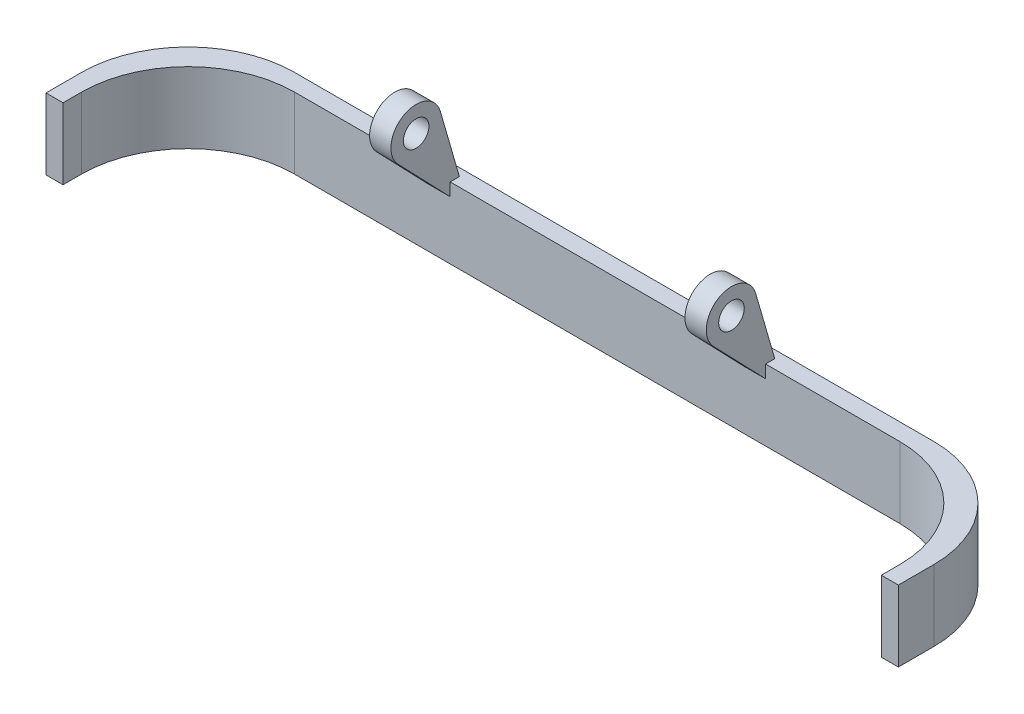
SolidWorks part; units mm, degrees
ref_plane "Front Plane" through (0, 0, 0) normal (0, 0, 1) x (1, 0, 0)
ref_plane "Top Plane" through (0, 0, 0) normal (0, 1, 0) x (1, 0, 0)
ref_plane "Right Plane" through (0, 0, 0) normal (1, 0, 0) x (0, 0, -1)
sketch "Sketch1" plane through (0, 0, 0) normal (0, 1, 0) x (1, 0, 0)
  line L0 (0, 0) -> (0, 5)
  line L1 (15, 20) -> (105, 20)
  line L2 (120, 5) -> (120, 0)
  line L8 (2.4, 0) -> (2.4, 2.6)
  line L9 (17.4, 17.6) -> (102.6, 17.6)
  line L10 (117.6, 2.6) -> (117.6, 0)
  line L11 (2.4, 0) -> (0, 0)
  line L12 (120, 0) -> (117.6, 0)
  line L13 (0, 20) -> (120, 20) construction
  line L14 (120, 20) -> (120, 0) construction
  line L15 (2.4, 17.6) -> (117.6, 17.6) construction
  line L16 (117.6, 17.6) -> (117.6, 0) construction
  line L17 (0, 0) -> (0, 20) construction
  line L18 (2.4, 0) -> (2.4, 17.6) construction
  arc A0 (105, 20) -> (120, 5) centre (105, 5) cw
  arc A1 (102.6, 17.6) -> (117.6, 2.6) centre (102.6, 2.6) cw
  arc A2 (0, 5) -> (15, 20) centre (15, 5) cw
  arc A3 (2.4, 2.6) -> (17.4, 17.6) centre (17.4, 2.6) cw
  dimension "D4" = 15
  dimension "D1" = 2.4
  dimension "D2" = 120
  dimension "D3" = 20
extrude "Boss-Extrude1" add sketch "Sketch1" along normal blind 10
ref_plane "Plane1" through (80.7, 0, 0) normal (1, 0, 0) x (0, 0, -1)
sketch "Sketch2" plane through (80.7, 0, 0) normal (1, 0, 0) x (0, 0, -1)
  line L0 (18.9, 10) -> (16.2186, 19.2849)
  line L1 (10.2497, 15.8388) -> (17.6, 8.1985)
  line L2 (17.6, 10) -> (17.6, 0) construction
  line L3 (20, 10) -> (5, 10) construction
  line L4 (17.6, 10) -> (17.6, 0)
  line L5 (17.6, 10) -> (18.9, 10)
  line L6 (12.808, 18.3) -> (17.6, 10) construction
  line L7 (16.4858, 9.3567) -> (18.7142, 10.6433) construction
  circle A0 centre (12.808, 18.3) radius 3.55
  circle A1 centre (12.808, 18.3) radius 1.75
  point P12 (17.6, 10)
  point P13 (12.8598, 18.3)
  point P14 (12.5744, 18.3)
  point P15 (0, 0)
  point P16 (0, 0)
  dimension "D2" = 3.5
  dimension "D3" = 1.8
  dimension "D4" = 8.3
  dimension "D5" = 120
  dimension "D6" = 1.1
extrude "Boss-Extrude2" add sketch "Sketch2" along normal blind 3 contours A0 L1 L0 | A0 A1 | A1 | A1 | A0 region at (80.7, 13.0524, -15.8219) region at (80.7, 18.7833, -16.2236) region at (80.7, 18.3, -12.808)
ref_plane "Plane2" through (39.3, 0, 0) normal (-1, 0, 0) x (0, 0, 1)
extrude "Boss-Extrude3" add sketch "Sketch2<3>" against normal blind 3 from surface contours A0 L1 L0 | A0 | A1 region at (80.7, 13.0524, -15.8219) region at (80.7, 18.7833, -16.2236) region at (80.7, 18.3, -12.808) starting at plane "Plane2"
sketch "Sketch2<3>" plane through (80.7, 0, 0) normal (1, 0, 0) x (0, 0, -1) same geometry as "Sketch2"
hole_wizard "M3 Clearance Hole1" positions "Sketch3" profile "Sketch4" hole size "M3" standard "ANSI Metric" end condition through all
sketch "Sketch3" plane through (83.7, 0, 0) normal (1, 0, 0) x (0, 0, -1)
  arc A0 (16.2186, 19.2849) -> (10.2497, 15.8388) centre (12.808, 18.3) ccw construction
  point P0 (12.808, 18.3)
sketch "Sketch4" plane through (83.7, 18.3, -12.808) normal (0, 1, 0) x (0, 0, -1)
  line L0 (0, 0) -> (0, 83.7)
  line L1 (0, 83.7) -> (1.8, 83.7)
  line L2 (1.8, 83.7) -> (1.8, 0)
  line L5 (1.8, 0) -> (0, 0)
  line L11 (0, -6.35) -> (0, 107.95) construction
  dimension "Thru Hole Dia." = 3.6
  dimension "Thru Hole Depth" = 83.7
